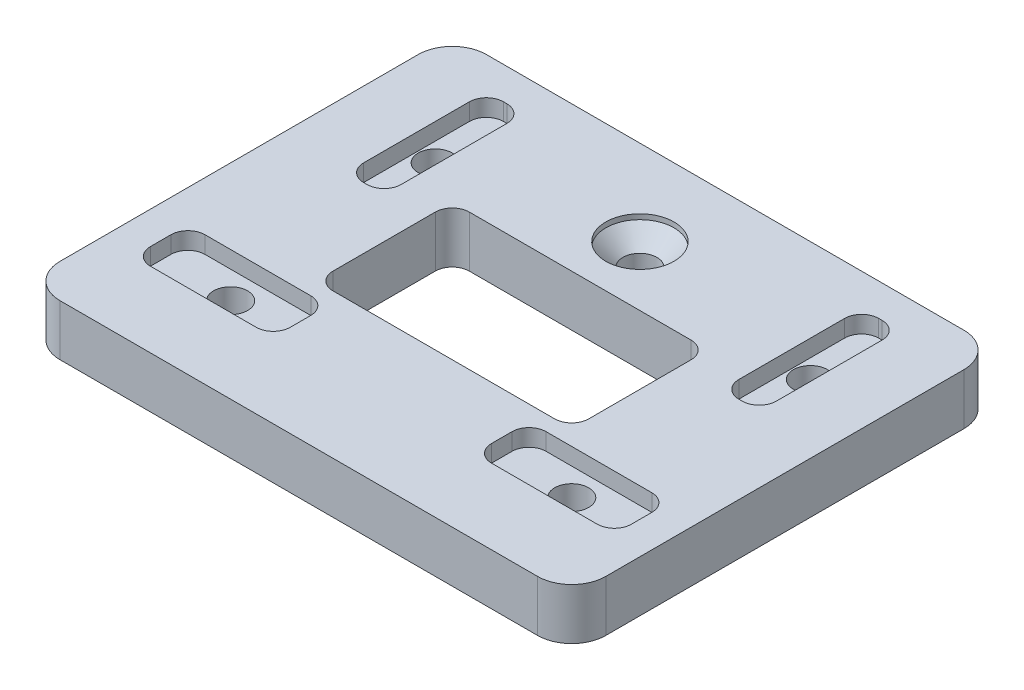
SolidWorks part; units mm, degrees
ref_plane "Front Plane" through (0, 0, 0) normal (0, 0, 1) x (1, 0, 0)
ref_plane "Top Plane" through (0, 0, 0) normal (0, 1, 0) x (1, 0, 0)
ref_plane "Right Plane" through (0, 0, 0) normal (1, 0, 0) x (0, 0, -1)
sketch "Sketch1" plane through (0, 0, 0) normal (0, 1, 0) x (1, 0, 0)
  line L1 (16, 12.5) -> (-16, 12.5)
  line L2 (16, 12.5) -> (16, -12.5)
  line L3 (16, -12.5) -> (-16, -12.5)
  line L4 (-16, 12.5) -> (-16, -12.5)
  line L5 (16, 12.5) -> (-16, -12.5) construction
  line L6 (16, -12.5) -> (-16, 12.5) construction
  point P0 (0, 0)
  dimension "D1" = 32
  dimension "D2" = 25
extrude "Boss-Extrude1" add sketch "Sketch1" along normal blind 3
sketch "Sketch2" plane through (0, 3, 0) normal (0, 1, 0) x (1, 0, 0)
  line L0 (-16, -6.5) -> (16, -6.5) construction
  line L1 (-16, 12.5) -> (-16, -12.5) construction
  line L2 (16, -12.5) -> (16, 12.5) construction
  line L3 (0, 12.5) -> (0, -12.5) construction
  line L4 (16, 12.5) -> (-16, 12.5) construction
  line L5 (-16, -12.5) -> (16, -12.5) construction
  line L6 (14.1, -5.9) -> (14.1, -7.1)
  line L7 (-13.1, -4.9) -> (-6.9, -4.9)
  line L8 (-14.1, -5.9) -> (-14.1, -7.1)
  line L9 (-13.1, -8.1) -> (-6.9, -8.1)
  line L10 (-5.9, -5.9) -> (-5.9, -7.1)
  line L11 (-14.1, -4.9) -> (-5.9, -8.1) construction
  line L12 (-14.1, -8.1) -> (-5.9, -4.9) construction
  line L13 (13.1, -4.9) -> (6.9, -4.9)
  line L14 (5.9, -5.9) -> (5.9, -7.1)
  line L15 (13.1, -8.1) -> (6.9, -8.1)
  line L16 (11.1, 10.6) -> (10.9, 10.6)
  line L17 (-11.1, 10.6) -> (-10.9, 10.6)
  line L18 (-12.1, 9.6) -> (-12.1, 3.4)
  line L19 (-11.1, 2.4) -> (-10.9, 2.4)
  line L20 (-9.9, 9.6) -> (-9.9, 3.4)
  line L21 (-12.1, 10.6) -> (-9.9, 2.4) construction
  line L22 (-12.1, 2.4) -> (-9.9, 10.6) construction
  line L23 (12.1, 9.6) -> (12.1, 3.4)
  line L24 (11.1, 2.4) -> (10.9, 2.4)
  line L25 (9.9, 9.6) -> (9.9, 3.4)
  arc A0 (-14.1, -7.1) -> (-13.1, -8.1) centre (-13.1, -7.1) ccw
  arc A1 (-6.9, -8.1) -> (-5.9, -7.1) centre (-6.9, -7.1) ccw
  arc A2 (-6.9, -4.9) -> (-5.9, -5.9) centre (-6.9, -5.9) cw
  arc A3 (-13.1, -4.9) -> (-14.1, -5.9) centre (-13.1, -5.9) ccw
  arc A4 (14.1, -7.1) -> (13.1, -8.1) centre (13.1, -7.1) cw
  arc A5 (13.1, -4.9) -> (14.1, -5.9) centre (13.1, -5.9) cw
  arc A6 (6.9, -4.9) -> (5.9, -5.9) centre (6.9, -5.9) ccw
  arc A7 (6.9, -8.1) -> (5.9, -7.1) centre (6.9, -7.1) cw
  arc A8 (-10.9, 2.4) -> (-9.9, 3.4) centre (-10.9, 3.4) ccw
  arc A9 (-12.1, 3.4) -> (-11.1, 2.4) centre (-11.1, 3.4) ccw
  arc A10 (-10.9, 10.6) -> (-9.9, 9.6) centre (-10.9, 9.6) cw
  arc A11 (-11.1, 10.6) -> (-12.1, 9.6) centre (-11.1, 9.6) ccw
  arc A12 (11.1, 10.6) -> (12.1, 9.6) centre (11.1, 9.6) cw
  arc A13 (12.1, 3.4) -> (11.1, 2.4) centre (11.1, 3.4) cw
  arc A14 (10.9, 2.4) -> (9.9, 3.4) centre (10.9, 3.4) cw
  arc A15 (10.9, 10.6) -> (9.9, 9.6) centre (10.9, 9.6) ccw
  point P12 (-10, -6.5)
  point P41 (-11, 6.5)
  dimension "D5" = 1
  dimension "D10" = 1
  dimension "D1" = 6
  dimension "D2" = 20
  dimension "D3" = 8.2
  dimension "D4" = 3.2
  dimension "D6" = 8.2
  dimension "D7" = 2.2
  dimension "D8" = 22
  dimension "D9" = 6
extrude "Cut-Extrude1" cut sketch "Sketch2" against normal blind 1
sketch "Sketch3" plane through (0, 2, 0) normal (0, 1, 0) x (1, 0, 0)
  line L0 (-10, -4.9) -> (-10, -8.1) construction
  line L1 (-6.9, -4.9) -> (-13.1, -4.9) construction
  line L2 (-13.1, -8.1) -> (-6.9, -8.1) construction
  line L3 (0, 12.5) -> (0, -12.5) construction
  line L4 (16, 12.5) -> (-16, 12.5) construction
  line L5 (-16, -12.5) -> (16, -12.5) construction
  line L6 (-12.1, 6.5) -> (-9.9, 6.5) construction
  line L7 (-12.1, 9.6) -> (-12.1, 3.4) construction
  line L8 (-9.9, 3.4) -> (-9.9, 9.6) construction
  circle A0 centre (-10, -6.5) radius 1
  circle A1 centre (10, -6.5) radius 1
  circle A2 centre (-11, 6.5) radius 1
  circle A3 centre (11, 6.5) radius 1
  dimension "D1" = 2
extrude "Cut-Extrude2" cut sketch "Sketch3" against normal up to next
sketch "Sketch4" plane through (0, 3, 0) normal (0, 1, 0) x (1, 0, 0)
  line L0 (0, 12.5) -> (0, -12.5) construction
  line L1 (16, 12.5) -> (-16, 12.5) construction
  line L2 (-16, -12.5) -> (16, -12.5) construction
  line L3 (-16, 0) -> (16, 0) construction
  line L6 (-16, 12.5) -> (-16, -12.5) construction
  line L7 (16, -12.5) -> (16, 12.5) construction
  circle A5 centre (0, 7.5) radius 1
  point P8 (0, 0)
  dimension "D1" = 2
  dimension "D2" = 5
extrude "Cut-Extrude3" cut sketch "Sketch4" against normal up to next
hole_wizard "CSK for M2 Flat Head Machine Screw4" positions "Sketch11" profile "Sketch12" countersink size "M2" standard "ANSI Metric" end condition up to next
sketch "Sketch11" plane through (0, 3, 0) normal (0, 1, 0) x (1, 0, 0)
  point P0 (0, 7.5)
  point P5 (0, 7.5)
sketch "Sketch12" plane through (0, 3, -7.5) normal (1, 0, 0) x (0, 0, 1)
  line L0 (0, 0) -> (0, 3)
  line L1 (0, 3) -> (1, 3)
  line L2 (1, 3) -> (1, 1.3)
  line L3 (1, 1.3) -> (2, 0.3)
  line L4 (2, 0.3) -> (2, 0)
  line L6 (2, 0) -> (0, 0)
  line L7 (-1, 1.3) -> (-2, 0.3) construction
  line L11 (0, -6.35) -> (0, 107.95) construction
  dimension "Thru Hole Dia." = 2
  dimension "Thru Hole Depth" = 3
  dimension "C'Sink Dia." = 4
  dimension "C'Sink Angle" = 90
  dimension "Head Clearance" = 0.3
fillet "Fillet1" radius 2 4 edges at (-16, 1.5, -12.5) (16, 1.5, -12.5) (16, 1.5, 12.5) (-16, 1.5, 12.5)
sketch "Sketch13" plane through (0, 3, 0) normal (0, 1, 0) x (1, 0, 0)
  line L1 (6.5, 4) -> (-6.5, 4)
  line L2 (7.5, 3) -> (7.5, -3)
  line L3 (6.5, -4) -> (-6.5, -4)
  line L4 (-7.5, 3) -> (-7.5, -3)
  line L5 (7.5, 4) -> (-7.5, -4) construction
  line L6 (7.5, -4) -> (-7.5, 4) construction
  arc A0 (6.5, 4) -> (7.5, 3) centre (6.5, 3) cw
  arc A1 (7.5, -3) -> (6.5, -4) centre (6.5, -3) cw
  arc A2 (-6.5, -4) -> (-7.5, -3) centre (-6.5, -3) cw
  arc A3 (-6.5, 4) -> (-7.5, 3) centre (-6.5, 3) ccw
  point P0 (0, 0)
  dimension "D3" = 1
  dimension "D1" = 15
  dimension "D2" = 8
extrude "Cut-Extrude4" cut sketch "Sketch13" against normal up to next
